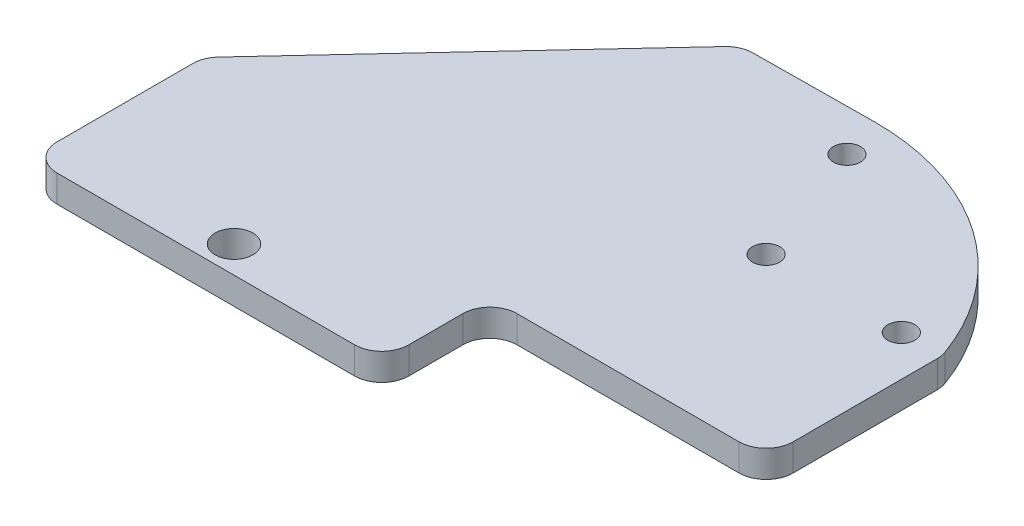
SolidWorks part; units mm, degrees
material "6061 Alloy"
ref_plane "Front Plane" through (0, 0, 0) normal (0, 0, 1) x (1, 0, 0)
ref_plane "Top Plane" through (0, 0, 0) normal (0, 1, 0) x (1, 0, 0)
ref_plane "Right Plane" through (0, 0, 0) normal (1, 0, 0) x (0, 0, -1)
sketch "Sketch1" plane through (0, 0, 0) normal (0, 1, 0) x (1, 0, 0)
  line L2 (5, 0) -> (87.1, 0)
  line L3 (97.1, 10) -> (97.1, 63.2972)
  line L4 (277.5177, 35) -> (97.1, 35) construction
  line L5 (277.5177, 35) -> (-135, 20.1354) construction
  line L6 (-5, -10) -> (-5, -30)
  line L7 (-15, -40) -> (-125, -40)
  line L8 (-135, -30) -> (-135, 20.1354)
  line L9 (-132.3211, 26.9473) -> (-42.1194, 123.8926)
  line L11 (-34.9535, 127.0795) -> (10.0465, 127.5)
  arc A0 (10.0465, 127.5) -> (96.5027, 66.7016) centre (9.8283, 35.3195) cw
  arc A1 (96.5027, 66.7016) -> (97.1, 63.2972) centre (87.1, 63.2972) cw
  arc A2 (87.1, 0) -> (97.1, 10) centre (87.1, 10) ccw
  arc A3 (-5, -10) -> (5, 0) centre (5, -10) cw
  arc A4 (-15, -40) -> (-5, -30) centre (-15, -30) ccw
  arc A5 (-125, -40) -> (-135, -30) centre (-125, -30) cw
  arc A6 (-135, 20.1354) -> (-132.3211, 26.9473) centre (-125, 20.1354) cw
  arc A7 (-42.1194, 123.8926) -> (-34.9535, 127.0795) centre (-34.7983, 117.0808) cw
  point P11 (-38.8619, 126.2179)
  point P14 (-134.3062, 23.7953)
  point P19 (97.1, 65)
  point P23 (97.1, 0)
  point P26 (-5, 0)
  point P29 (-5, -40)
  point P32 (-135, -40)
  point P35 (-135, 24.0681)
  dimension "D1" = 10
  dimension "D7" = 10
  dimension "D9" = 92.1807
  dimension "D2" = 127.5
  dimension "D3" = 45
  dimension "D4" = 65
  dimension "D5" = 35
  dimension "D6" = 45
  dimension "D8" = 140
sketch "Sketch2" plane through (0, 0, 0) normal (0, 1, 0) x (1, 0, 0)
  line L0 (14.999, 111.9846) -> (32.1, 65) construction
  line L1 (32.1, 65) -> (82.1, 65) construction
  line L2 (32.1, 65) -> (43.9894, 32.3341) construction
  line L3 (30.6144, 27.466) -> (57.3644, 37.2022) construction
  line L4 (277.5177, 35) -> (97.1, 35) construction
  circle A0 centre (14.999, 111.9846) radius 5
  circle A1 centre (82.1, 65) radius 5
  circle A2 centre (32.1, 65) radius 5
  point P9 (43.9894, 32.3341)
  dimension "D1" = 50
  dimension "D2" = 50
  dimension "D4" = 110
  dimension "D5" = 7.534
extrude "Boss-Extrude1" add sketch "Sketch1" along normal blind 10
extrude "Cut-Extrude4" cut sketch "Sketch2" against normal through all and the other way through all
sketch "Sketch3" plane through (0, 0, 0) normal (0, -1, 0) x (1, 0, 0)
  line L0 (-125, 40) -> (-15, 40) construction
  line L1 (-69.6154, 30) -> (-135, 30) construction
  line L2 (-135, -20.1354) -> (-135, 30) construction
  line L3 (-69.6154, 30) -> (-5, 20) construction
  line L4 (-5, 30) -> (-5, 10) construction
  circle A0 centre (-69.6154, 30) radius 7
  dimension "D1" = 10
extrude "Cut-Extrude5" cut sketch "Sketch3" against normal through all
